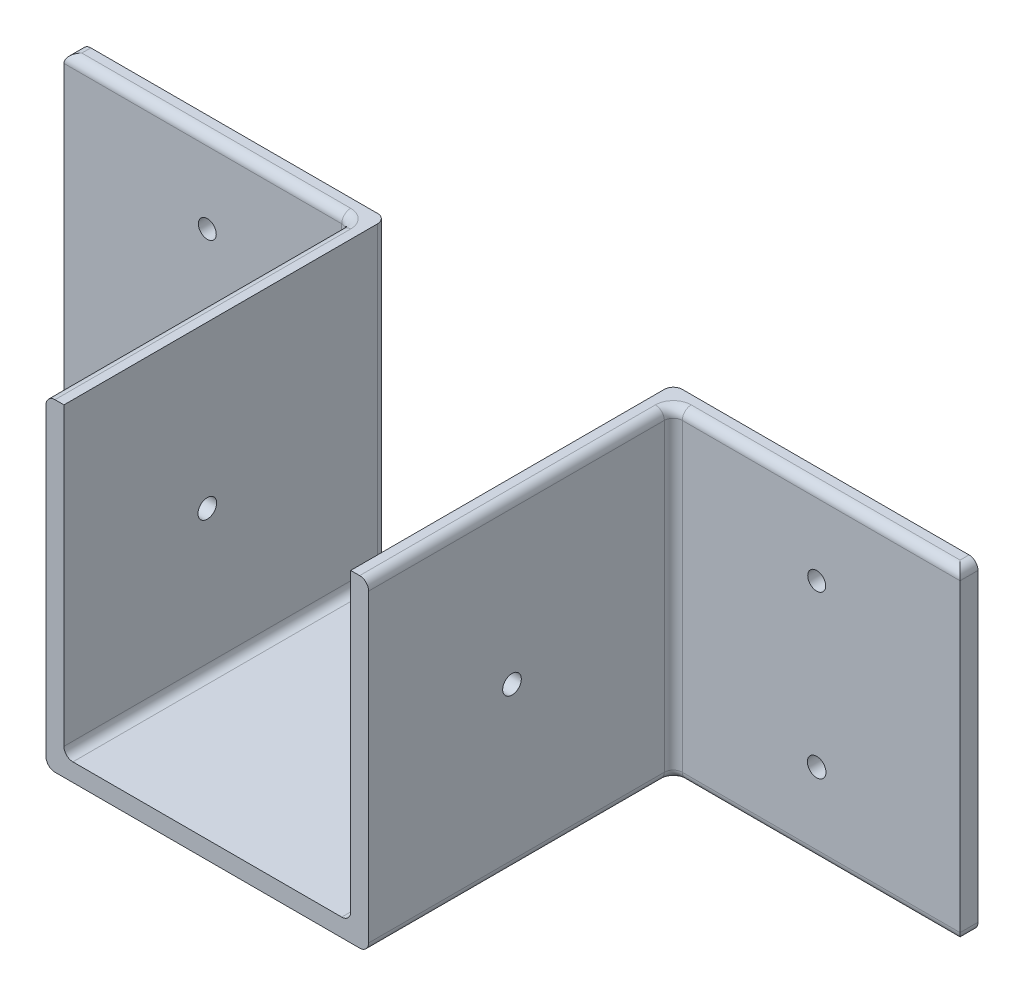
SolidWorks part; units mm, degrees
material "1060 Alloy"
ref_plane "Front Plane" through (0, 0, 0) normal (0, 0, 1) x (1, 0, 0)
ref_plane "Top Plane" through (0, 0, 0) normal (0, 1, 0) x (1, 0, 0)
ref_plane "Right Plane" through (0, 0, 0) normal (1, 0, 0) x (0, 0, -1)
sketch "Sketch1" plane through (0, 0, 0) normal (0, 0, 1) x (1, 0, 0)
  line L9 (0, 0) -> (-79.375, 0)
  line L10 (0, 0) -> (0, 57.15)
  line L11 (0, 57.15) -> (-79.375, 57.15)
  line L12 (-79.375, 0) -> (-79.375, 57.15)
  line L13 (-25.4, 53.975) -> (-25.4, 3.175)
  line L14 (-25.4, 3.175) -> (0, 3.175)
  line L15 (0, 3.175) -> (-25.4, 3.175)
  line L16 (-28.575, 0) -> (-28.575, 57.15)
  line L17 (-28.575, 28.575) -> (-79.375, 28.575) construction
  line L18 (-53.975, 28.575) -> (-53.975, 57.15) construction
  line L19 (-53.975, 28.575) -> (-53.975, 0) construction
  line L20 (-25.4, 53.975) -> (-25.4, 57.15)
  circle A2 centre (-53.975, 42.8625) radius 1.5875
  circle A3 centre (-53.975, 14.2875) radius 1.651
  point P19 (-53.975, 14.2875)
  point P22 (-53.975, 42.8625)
  dimension "D6" = 3.175
  dimension "D7" = 3.302
  dimension "D1" = 25.4
  dimension "D2" = 50.8
  dimension "D3" = 3.175
  dimension "D5" = 3.175
  dimension "D8" = 50.8
extrude "Boss-Extrude1" add sketch "Sketch1" along normal blind 57.15 contours L16 L9 L10 L14 L13 L11 region at (-14.2875, 0.639, 0)
extrude "Boss-Extrude2" add sketch "Sketch1<3>" along normal blind 3.175 contours L9 L16 L11 L12 A3 A2 region at (-53.975, 28.5782, 0)
sketch "Sketch1<3>" plane through (0, 0, 0) normal (0, 0, 1) x (1, 0, 0) same geometry as "Sketch1"
sketch "Sketch2" plane through (-28.575, 0, 0) normal (-1, 0, 0) x (0, 0, 1)
  line L0 (31.75, 57.15) -> (31.75, 0) construction
  line L1 (57.15, 57.15) -> (3.175, 57.15) construction
  line L2 (57.15, 0) -> (3.175, 0) construction
  line L3 (57.15, 0) -> (57.15, 57.15) construction
  circle A0 centre (31.75, 28.575) radius 1.651
  dimension "D1" = 3.302
  dimension "D2" = 25.4
extrude "Cut-Extrude1" cut sketch "Sketch2" against normal up to surface (3.175 mm away) contours A0 up to face at (-25.4, 30.1625, 28.575)
fillet "Fillet1" radius 1.5875 10 edges at (-53.975, 0, 3.175) (-53.975, 57.15, 3.175) (-25.4, 3.175, 28.575) (-79.375, 0, 1.5875) (-28.575, 0, 30.1625) (-28.575, 28.575, 3.175) (-28.575, 57.15, 30.1625) (-79.375, 57.15, 1.5875) (-12.7, 3.175, 0) (-25.4, 30.1625, 0)
ref_plane "Plane1" through (0, 0, 0) normal (1, 0, 0) x (0, 0, -1)
mirror "Mirror1" about plane through (0, 0, 0) normal (1, 0, 0) of "Boss-Extrude1", "Cut-Extrude1", "Fillet1", "Boss-Extrude2"
equation "\"sheet_thickness\" = 1 / 8in'Universal thickness of a metal sheet"
equation "\"offset_visible_hidden\" = 0.5in'The distance between the outter and inner shell"
equation "\"hole_size_STD\" = 1 / 8in'Standard hole size"
equation "\"fillet_radius\"= 1 / 16in'Standard fillet radius"
equation "\"visible_side\"= 2in'The side of a square bracket"
equation "\"D1@Sketch1\"=\"visible_side\"/2"
equation "\"D3@Sketch1\"=\"sheet_thickness\""
equation "\"D5@Sketch1\"=\"sheet_thickness\""
equation "\"D6@Sketch1\"=\"hole_size_STD\""
equation "\"D2@Sketch1\"=\"visible_side\""
equation "\"D1@Boss-Extrude2\"=\"sheet_thickness\""
equation "\"D1@Fillet1\"=\"fillet_radius\""
